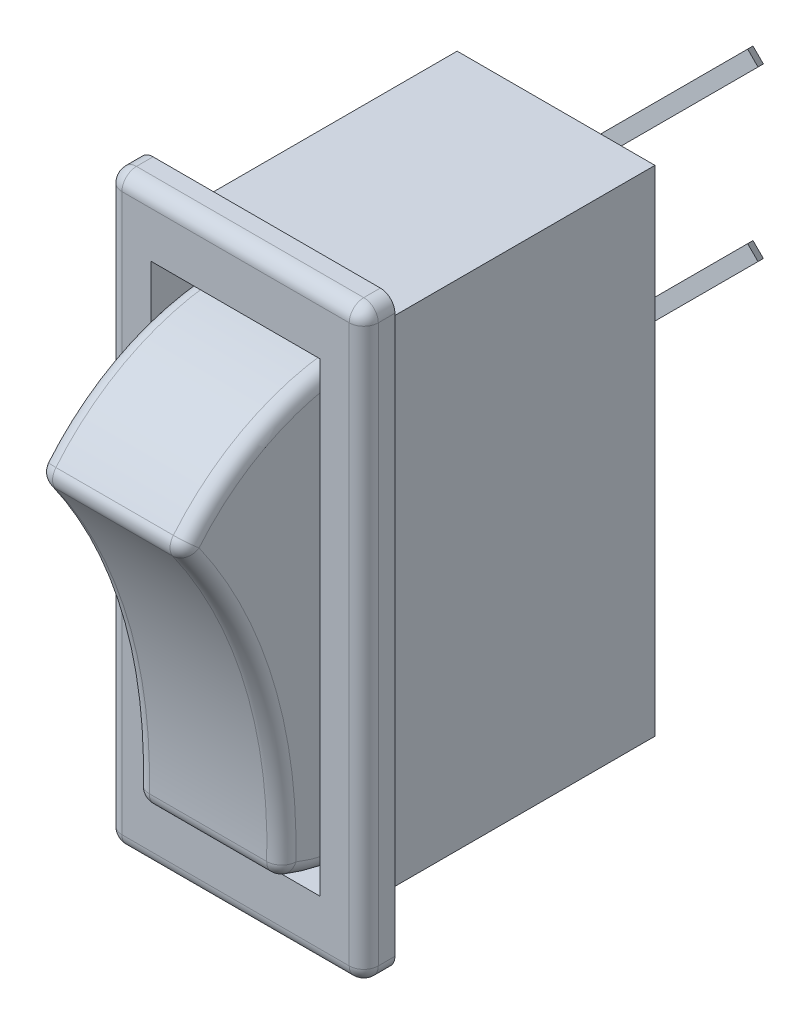
SolidWorks part; units mm, degrees
material "ABS"
ref_plane "Front Plane" through (0, 0, 0) normal (0, 0, 1) x (1, 0, 0)
ref_plane "Top Plane" through (0, 0, 0) normal (0, 1, 0) x (1, 0, 0)
ref_plane "Right Plane" through (0, 0, 0) normal (1, 0, 0) x (0, 0, -1)
sketch "Sketch1" plane through (0, 0, 0) normal (0, 0, 1) x (1, 0, 0)
  line L0 (0, -55) -> (0, 55) construction
  line L1 (-5.4, 13.5) -> (5.4, 13.5)
  line L2 (-5.4, 13.5) -> (-5.4, -13.5)
  line L3 (-5.4, -13.5) -> (5.4, -13.5)
  line L4 (5.4, 13.5) -> (5.4, -13.5)
  line L5 (55, 0) -> (-55, 0) construction
  point P4 (0, 13.5)
  point P7 (-5.4, 0)
  dimension "D1" = 10.8
  dimension "D2" = 27
extrude "main body" add sketch "Sketch1" against normal blind 15.8
sketch "Sketch2" plane through (0, 0, 0) normal (0, 0, 1) x (1, 0, 0)
  line L4 (-5.4, 13.5) -> (-5.4, -13.5)
  line L5 (-5.4, -13.5) -> (5.4, -13.5)
  line L6 (5.4, -13.5) -> (5.4, 13.5)
  line L7 (5.4, 13.5) -> (-5.4, 13.5)
  line L8 (-5.4, 13.5) -> (-5.4, -13.5) construction
  line L9 (-5.4, -13.5) -> (5.4, -13.5) construction
  line L10 (5.4, -13.5) -> (5.4, 13.5) construction
  line L11 (5.4, 13.5) -> (-5.4, 13.5) construction
  line L16 (-4.6063, 12.7063) -> (-4.6063, -12.7063)
  line L17 (-4.6063, -12.7063) -> (4.6063, -12.7062)
  line L18 (4.6063, -12.7062) -> (4.6063, 12.7062)
  line L19 (4.6063, 12.7062) -> (-4.6063, 12.7063)
  line L20 (-4.6063, 12.7063) -> (-4.6063, -12.7063)
  line L21 (-4.6063, -12.7063) -> (4.6063, -12.7062)
  line L22 (4.6063, -12.7062) -> (4.6063, 12.7062)
  line L23 (4.6063, 12.7062) -> (-4.6063, 12.7063)
  dimension "D1" = 0
  dimension "D2" = 0.7937
extrude "main body light" cut sketch "Sketch2" against normal offset from surface (13.8 mm away) 2 up to face at (0, 0, -15.8)
sketch "Sketch3" plane through (0, 0, 0) normal (0, 0, 1) x (1, 0, 0)
  line L0 (0, -55) -> (0, 55) construction
  line L1 (-7, 16) -> (7, 16)
  line L2 (-7, 16) -> (-7, -16)
  line L3 (-7, -16) -> (7, -16)
  line L4 (7, 16) -> (7, -16)
  line L5 (55, 0) -> (-55, 0) construction
  line L6 (-4.6063, 12.7063) -> (4.6063, 12.7062)
  line L7 (4.6063, 12.7062) -> (4.6063, -12.7063)
  line L8 (-4.6063, -12.7063) -> (4.6063, -12.7063)
  line L9 (-4.6063, 12.7063) -> (-4.6063, -12.7063)
  line L11 (-4.6063, -12.7063) -> (4.6063, -12.7063) construction
  point P4 (0, 16)
  point P7 (-7, 0)
  point P14 (-4.6063, 0)
  point P15 (0, 12.7062)
  dimension "D1" = 14
  dimension "D2" = 32
extrude "flange" add sketch "Sketch3" along normal blind 1.7
sketch "Sketch4" plane through (0, 0, 0) normal (1, 0, 0) x (0, 0, -1)
  line L0 (6.0061, 2.3799) -> (8.5092, 0)
  line L1 (1.315, 10.7558) -> (8.5092, 0)
  line L2 (-1.7, -16) -> (0, -16) construction
  line L3 (55, 0) -> (-55, 0) construction
  line L4 (-8.685, 6.475) -> (-8.685, -1.9309) construction
  line L5 (2.4148, 0) -> (4.3189, 0) construction
  line L6 (0, -16) -> (0, 16) construction
  line L7 (-1.7, -16) -> (-1.7, 16) construction
  line L8 (-1.7, 16) -> (0, 16) construction
  line L10 (1.315, 15.4459) -> (1.315, -1.9309) construction
  line L11 (1.315, 6.475) -> (1.315, -1.9309) construction
  line L12 (13.8, 12.7062) -> (-1.7, 12.7062) construction
  line L13 (-4.4079, -2.0715) -> (1.4827, -1.1347) construction
  arc A0 (-8.685, 6.475) -> (-3.224, -11.555) centre (-31.4545, -10.2635) cw
  arc A1 (-8.685, 6.475) -> (0, 11.4784) centre (1.4827, -1.1347) cw
  circle A3 centre (2.4148, 0) radius 1.5875
  arc A4 (0, 11.4784) -> (1.315, 10.7558) centre (-5.4479, 0.0062) cw
  arc A5 (5.5257, -11.83) -> (6.0061, 2.3799) centre (-4.752, -4.3695) ccw
  arc A6 (-3.224, -11.555) -> (5.5257, -11.83) centre (1.4827, -1.1347) ccw
  point P12 (-0.85, 16)
  dimension "D1" = 28.26
  dimension "D6" = 12.7
  dimension "D7" = 4.1148
  dimension "D8" = 3.175
  dimension "D2" = 6.985
  dimension "D3" = 9.525
  dimension "D4" = 1.524
  dimension "D5" = 4.445
  dimension "D9" = 10
  dimension "D10" = 167.332
  dimension "D11" = 12.9401
extrude "switch body and profile" add sketch "Sketch4" along normal mid plane 8 separate body
fillet "Fillet1" radius 0.7937 8 edges at (-7, -16, 0.85) (7, -16, 0.85) (-7, 16, 0.85) (7, 16, 0.85) (-7, 0, 1.7) (0, -16, 1.7) (7, 0, 1.7) (0, 16, 1.7)
fillet "Fillet2" radius 0.7937 8 edges at (0, 6.475, 8.685) (-4, -12.563, -1.1235) (4, -12.563, -1.1235) (0, -11.555, 3.224) (-4, -2.0715, 4.4079) (4, -2.0715, 4.4079) (4, 9.8698, 4.857) (-4, 9.8698, 4.857)
sketch "Sketch5" plane through (0, 0, -15.8) normal (0, 0, -1) x (-1, 0, 0)
  line L0 (-2.5279, 3.2622) -> (1.9622, -1.2279)
  line L1 (-2.5279, 3.2622) -> (-1.9622, 3.8279)
  line L2 (1.9622, -1.2279) -> (2.5279, -0.6622)
  line L3 (-1.9622, 3.8279) -> (2.5279, -0.6622)
  line L4 (-2.5279, 3.2622) -> (2.5279, -0.6622) construction
  line L6 (1.9622, -1.2279) -> (-1.9622, 3.8279) construction
  line L7 (-2.5279, 12.4622) -> (1.9622, 7.9721)
  line L8 (-2.5279, 12.4622) -> (-1.9622, 13.0279)
  line L9 (1.9622, 7.9721) -> (2.5279, 8.5378)
  line L10 (-1.9622, 13.0279) -> (2.5279, 8.5378)
  line L11 (-2.5279, 12.4622) -> (2.5279, 8.5378) construction
  line L12 (1.9622, 7.9721) -> (-1.9622, 13.0279) construction
  line L13 (5.4, -13.5) -> (-5.4, -13.5) construction
  line L14 (-5.4, 13.5) -> (5.4, 13.5) construction
  point P1 (0, 1.3)
  point P2 (0, 10.5)
  dimension "D1" = 9.2
  dimension "D2" = 0.8
  dimension "D3" = 6.35
  dimension "D4" = 45
  dimension "D5" = 3
extrude "Extrude5" add sketch "Sketch5" along normal blind 9.5
chamfer "Chamfer1" distance 1 angle 45 4 edges at (2.2451, 12.7451, -25.3) (-2.2451, 8.2549, -25.3) (2.2451, 3.5451, -25.3) (-2.2451, -0.9451, -25.3)
